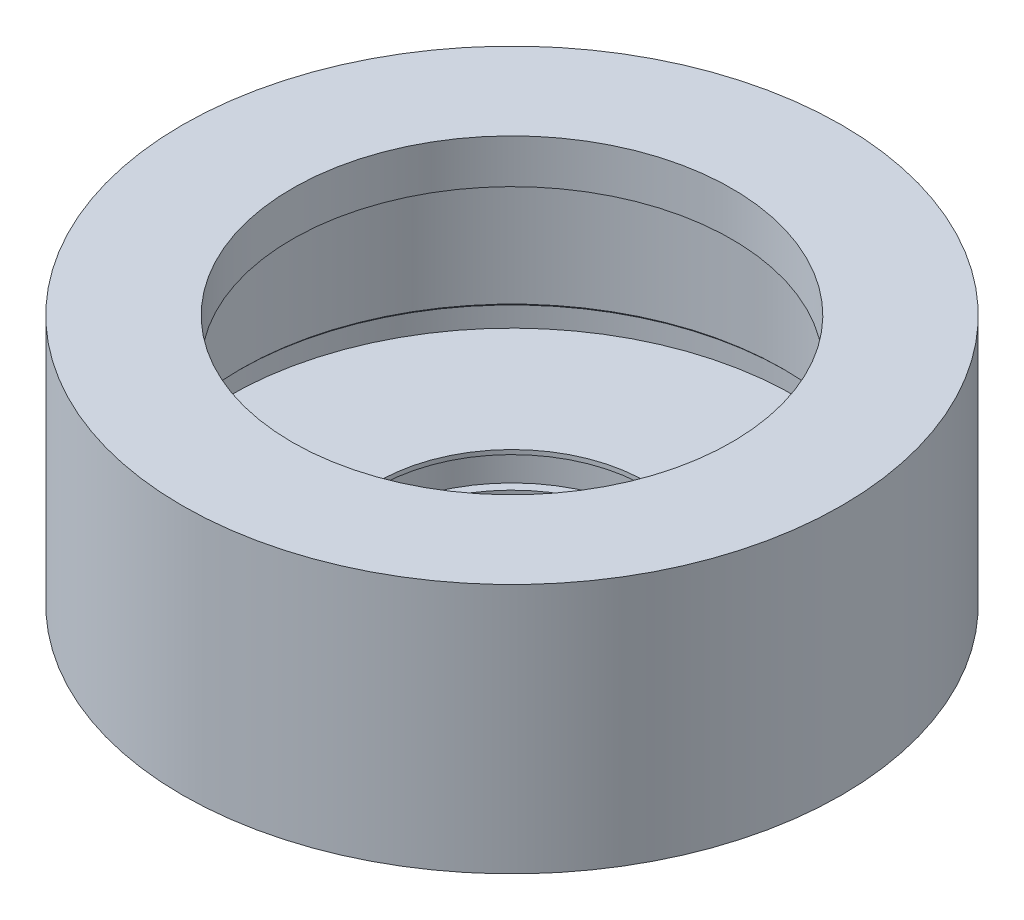
SolidWorks part; units mm, degrees
ref_plane "Front Plane" through (0, 0, 0) normal (0, 0, 1) x (1, 0, 0)
ref_plane "Top Plane" through (0, 0, 0) normal (0, 1, 0) x (1, 0, 0)
ref_plane "Right Plane" through (0, 0, 0) normal (1, 0, 0) x (0, 0, -1)
ref_axis "Axis1" through (0, 19.75, 0) along (0, -1, 0)
sketch "Sketch1" plane through (0, 0, 0) normal (0, 1, 0) x (1, 0, 0)
  circle A0 centre (0, 0) radius 75
  circle A1 centre (0, 0) radius 61.6875
  dimension "D1" = 150
  dimension "D2" = 123.375
extrude "Gear Boss" add sketch "Sketch1" along normal mid plane 25
chamfer "Tooth Corner Chamfer" distance 0.6 angle 45 2 edges at (0, -12.5, 61.6875) (0, 12.5, 61.6875)
sketch "Sketch2" [suppressed] plane through (0, 0, 0) normal (0, 1, 0) x (1, 0, 0)
  line L0 (0, 0) -> (64.0281, 1.6766)
  line L1 (0, 0) -> (64.0281, -1.6766)
  line L2 (0, 0) -> (64.05, 0) construction
  circle A0 centre (0, 0) radius 59.2006
  circle A1 centre (0, 0) radius 64.05
  spline S0 degree 4 poles (59.2005, -0.1074) (59.208, -0.1074) (59.2289, -0.107) (59.2685, -0.1056) (59.3331, -0.1021) (59.4155, -0.0959) (59.522, -0.0861) (59.6474, -0.072) (59.7854, -0.054) (59.9356, -0.0315) (60.0854, -0.0067) (60.235, 0.0204) (60.3841, 0.0495) (60.5647, 0.0872) (60.7815, 0.1358) (61.0349, 0.1977) (61.3226, 0.2737) (61.616, 0.3576) (61.9049, 0.4454) (62.1971, 0.5401) (62.48, 0.636) (62.7741, 0.7418) (63.0457, 0.8427) (63.3503, 0.9626) (63.5963, 1.0613) (63.9211, 1.1989) (64.113, 1.2824) (64.3378, 1.3827) (64.4377, 1.4285) (64.4992, 1.4568) knots 0 0 0 0 0 0.005377 0.015084 0.028532 0.04661 0.064855 0.092111 0.119476 0.146842 0.174209 0.201575 0.228941 0.256307 0.307035 0.361767 0.4165 0.471232 0.525964 0.580697 0.635429 0.690161 0.744894 0.799626 0.854358 0.909091 0.954545 1 1 1 1 1 construction
  spline S1 degree 4 poles (59.2005, -0.1074) (59.208, -0.1074) (59.2289, -0.107) (59.2685, -0.1056) (59.3331, -0.1021) (59.4155, -0.0959) (59.522, -0.0861) (59.6474, -0.072) (59.7854, -0.054) (59.9356, -0.0315) (60.0854, -0.0067) (60.235, 0.0204) (60.3841, 0.0495) (60.5647, 0.0872) (60.7815, 0.1358) (61.0349, 0.1977) (61.3226, 0.2737) (61.616, 0.3576) (61.9049, 0.4454) (62.1971, 0.5401) (62.48, 0.636) (62.7741, 0.7418) (63.0457, 0.8427) (63.3503, 0.9626) (63.5963, 1.0613) (63.8506, 1.1691) (63.9745, 1.2224) (64.0378, 1.25) knots 0 0 0 0 0 0.005377 0.015084 0.028532 0.04661 0.064855 0.092111 0.119476 0.146842 0.174209 0.201575 0.228941 0.256307 0.307035 0.361767 0.4165 0.471232 0.525964 0.580697 0.635429 0.690161 0.744894 0.799626 0.854358 0.909091 0.909091 0.909091 0.909091 0.909091
  spline S2 degree 4 poles (59.2005, 0.1074) (59.208, 0.1074) (59.2289, 0.107) (59.2685, 0.1056) (59.3331, 0.1021) (59.4155, 0.0959) (59.522, 0.0861) (59.6474, 0.072) (59.7854, 0.054) (59.9356, 0.0315) (60.0854, 0.0067) (60.235, -0.0204) (60.3841, -0.0495) (60.5647, -0.0872) (60.7815, -0.1358) (61.0349, -0.1977) (61.3226, -0.2737) (61.616, -0.3576) (61.9049, -0.4454) (62.1971, -0.5401) (62.48, -0.636) (62.7741, -0.7418) (63.0457, -0.8427) (63.3503, -0.9626) (63.5963, -1.0613) (63.9211, -1.1989) (64.113, -1.2824) (64.3378, -1.3827) (64.4377, -1.4285) (64.4992, -1.4568) knots 0 0 0 0 0 0.005377 0.015084 0.028532 0.04661 0.064855 0.092111 0.119476 0.146842 0.174209 0.201575 0.228941 0.256307 0.307035 0.361767 0.4165 0.471232 0.525964 0.580697 0.635429 0.690161 0.744894 0.799626 0.854358 0.909091 0.954545 1 1 1 1 1 construction
  spline S3 degree 4 poles (59.2005, 0.1074) (59.208, 0.1074) (59.2289, 0.107) (59.2685, 0.1056) (59.3331, 0.1021) (59.4155, 0.0959) (59.522, 0.0861) (59.6474, 0.072) (59.7854, 0.054) (59.9356, 0.0315) (60.0854, 0.0067) (60.235, -0.0204) (60.3841, -0.0495) (60.5647, -0.0872) (60.7815, -0.1358) (61.0349, -0.1977) (61.3226, -0.2737) (61.616, -0.3576) (61.9049, -0.4454) (62.1971, -0.5401) (62.48, -0.636) (62.7741, -0.7418) (63.0457, -0.8427) (63.3503, -0.9626) (63.5963, -1.0613) (63.8506, -1.1691) (63.9745, -1.2224) (64.0378, -1.25) knots 0 0 0 0 0 0.005377 0.015084 0.028532 0.04661 0.064855 0.092111 0.119476 0.146842 0.174209 0.201575 0.228941 0.256307 0.307035 0.361767 0.4165 0.471232 0.525964 0.580697 0.635429 0.690161 0.744894 0.799626 0.854358 0.909091 0.909091 0.909091 0.909091 0.909091
  dimension "D1" = 128.1
  dimension "D2" = 118.4013
  dimension "D3" = 3
extrude "Tooth Cut" [suppressed] cut sketch "Sketch2" against normal through all both and the other way through all contours A0 S3 S1 A1 L0 | S3 S1 A0 L1 A1 | S3 A0 S1
sketch "Sketch3" [suppressed] plane through (0, 0, 0) normal (0, 1, 0) x (1, 0, 0)
  line L0 (64.0378, 1.25) -> (64.298, 1.3635)
  line L1 (64.0281, 1.6766) -> (64.2905, 1.6835)
  line L2 (64.298, -1.3635) -> (64.0378, -1.25)
  line L3 (62.2662, -1.6305) -> (64.0281, -1.6766) construction
  line L4 (64.0281, -1.6766) -> (64.2905, -1.6835)
  line L5 (62.2662, 1.6305) -> (64.0281, 1.6766) construction
  arc A0 (64.2905, -1.6835) -> (64.298, -1.3635) centre (0, 0) ccw
  arc A1 (64.0281, -1.6766) -> (64.0378, -1.25) centre (0, 0) ccw
  arc A2 (64.0378, 1.25) -> (64.0281, 1.6766) centre (0, 0) ccw construction
  arc A3 (64.0378, 1.25) -> (64.0281, 1.6766) centre (0, 0) ccw
  arc A4 (64.298, 1.3635) -> (64.2905, 1.6835) centre (0, 0) ccw
  spline S0 degree 4 poles (62.2849, -0.5703) (62.2983, -0.5749) (62.3833, -0.6036) (62.5397, -0.6575) (62.7741, -0.7418) (63.0457, -0.8427) (63.3503, -0.9626) (63.5963, -1.0613) (63.8506, -1.1691) (63.9745, -1.2224) (64.0378, -1.25) knots 0.570424 0.570424 0.570424 0.570424 0.570424 0.580697 0.635429 0.690161 0.744894 0.799626 0.854358 0.909091 0.909091 0.909091 0.909091 0.909091 construction
  spline S1 degree 4 poles (62.2849, 0.5703) (62.2983, 0.5749) (62.3833, 0.6036) (62.5397, 0.6575) (62.7741, 0.7418) (63.0457, 0.8427) (63.3503, 0.9626) (63.5963, 1.0613) (63.8506, 1.1691) (63.9745, 1.2224) (64.0378, 1.25) knots 0.570424 0.570424 0.570424 0.570424 0.570424 0.580697 0.635429 0.690161 0.744894 0.799626 0.854358 0.909091 0.909091 0.909091 0.909091 0.909091 construction
  dimension "D1" = 128.625
extrude "Root Clearance" [suppressed] cut sketch "Sketch3" against normal through all both and the other way through all
fillet "Root Fillet" [suppressed] radius 0.3523
pattern_circular "CirPattern1" [suppressed] count 120 over 360 about axis through (0, 19.75, 0) along (0, -1, 0) of bodies 103
sketch "Pitch Circle" plane through (0, 0, 0) normal (0, 1, 0) x (1, 0, 0)
  circle A0 centre (0, 0) radius 63
  dimension "D1" = 126
sketch "Sketch8" plane through (0, 0, 0) normal (1, 0, 0) x (0, 0, -1)
  line L0 (30.5, -18.5) -> (64.3125, -18.5)
  line L1 (50, 29.5) -> (75, 29.5)
  line L2 (50, 29.5) -> (50, 19.5)
  line L3 (50, 19.5) -> (64.3125, 19.5)
  line L4 (75, 29.5) -> (75, 12.5)
  line L5 (75, -12.5) -> (75, -27.5)
  line L6 (75, -27.5) -> (30.5, -27.5)
  line L7 (30.5, -27.5) -> (30.5, -26.5)
  line L8 (30.5, -26.5) -> (32.5, -26.5)
  line L9 (32.5, -26.5) -> (32.5, -19.5)
  line L10 (32.5, -19.5) -> (30.5, -19.5)
  line L11 (30.5, -19.5) -> (30.5, -18.5)
  line L12 (0, 19.75) -> (0, -29.75) construction
  line L13 (64.3125, -12.5) -> (75, -12.5)
  line L14 (64.3125, -18.5) -> (64.3125, -12.5)
  line L15 (64.3125, 19.5) -> (64.3125, 12.5)
  line L16 (64.3125, 12.5) -> (75, 12.5)
  line L17 (75, -12.5) -> (75, 12.5) construction
  line L18 (0, 0) -> (75, 0) construction
  dimension "D2" = 7
  dimension "D3" = 1
  dimension "D4" = 32.5
  dimension "D5" = 2
  dimension "D6" = 50
  dimension "D8" = 75
  dimension "D9" = 25
  dimension "D1" = 7
  dimension "D10" = 7
  dimension "D11" = 64.3125
  dimension "D12" = 1
  dimension "D7" = 10
revolve "Revolve1" add sketch "Sketch8" angle 360 about axis through (0, 19.75, 0) along (0, -1, 0)
equation "\"ringGearToothCount\" = 120"
equation "\"sunGearToothCount\" = 36"
equation "\"planetGearToothCount\" = (\"ringGearToothCount\" - \"sunGearToothCount\") / 2"
equation "\"faceWidth\" = 25mm"
equation "\"module\" = 1.05"
equation "\"pressureAngle\" = 20deg"
equation "\"toothCount\"= \"ringGearToothCount\""
equation "\"pitchAngle\" = 360deg / \"toothCount\""
equation "\"pitchDiameter\" = \"module\" * \"toothCount\""
equation "\"pitchRadius\" = \"pitchDiameter\" / 2"
equation "\"baseDiameter\" = \"pitchDiameter\" * cos(\"pressureAngle\")"
equation "\"baseRadius\" = \"baseDiameter\" / 2"
equation "\"addendum\"= - 1.25 * \"module\""
equation "\"dedendum\"= - 1.0 * \"module\""
equation "\"rootClearance\"= - 0.25 * \"module\""
equation "\"addendumDiameter\" = \"pitchDiameter\" + 2 * \"addendum\""
equation "\"addendumRadius\" = \"addendumDiameter\" / 2"
equation "\"dedendumDiameter\" = \"pitchDiameter\" - 2 * \"dedendum\""
equation "\"dedendumRadius\" = \"dedendumDiameter\" / 2"
equation "\"rootDiameter\" = \"dedendumDiameter\" - 2 * \"rootClearance\""
equation "\"rootRadius\" = \"rootDiameter\" / 2"
equation "\"dedendumFilletRadius\" = abs(\"rootClearance\") * cos(\"pressureAngle\") * tan((90 + \"pressureAngle\") / 2)"
equation "\"alpha\" = sqr(\"pitchDiameter\"^2 - \"baseDiameter\"^2) / \"baseDiameter\" * 180 / PI - \"pressureAngle\""
equation "\"beta\" = \"pitchAngle\" / 4 - \"alpha\""
equation "\"phi\"= sqr ( \"dedendumRadius\" ^ 2 - \"baseRadius\" ^ 2 ) / \"baseRadius\""
equation "\"betaR\" = \"beta\" * PI / 180"
equation "\"D2@Sketch1\"=\"addendumDiameter\""
equation "\"D1@Gear Boss\" = \"faceWidth\""
equation "\"D1@Sketch2\"=\"dedendumDiameter\""
equation "\"D2@Sketch2\"=\"baseDiameter\""
equation "\"D3@Sketch2\"=\"pitchAngle\""
equation "\"D1@Root Fillet\"=\"dedendumFilletRadius\""
equation "\"D1@Sketch3\"=\"rootDiameter\""
equation "\"D1@CirPattern1\"=\"toothCount\""
equation "\"D1@Pitch Circle\" = \"pitchDiameter\""
equation "\"D9@Sketch8\"=\"faceWidth\""
equation "\"D11@Sketch8\"=\"rootDiameter\"/2"
